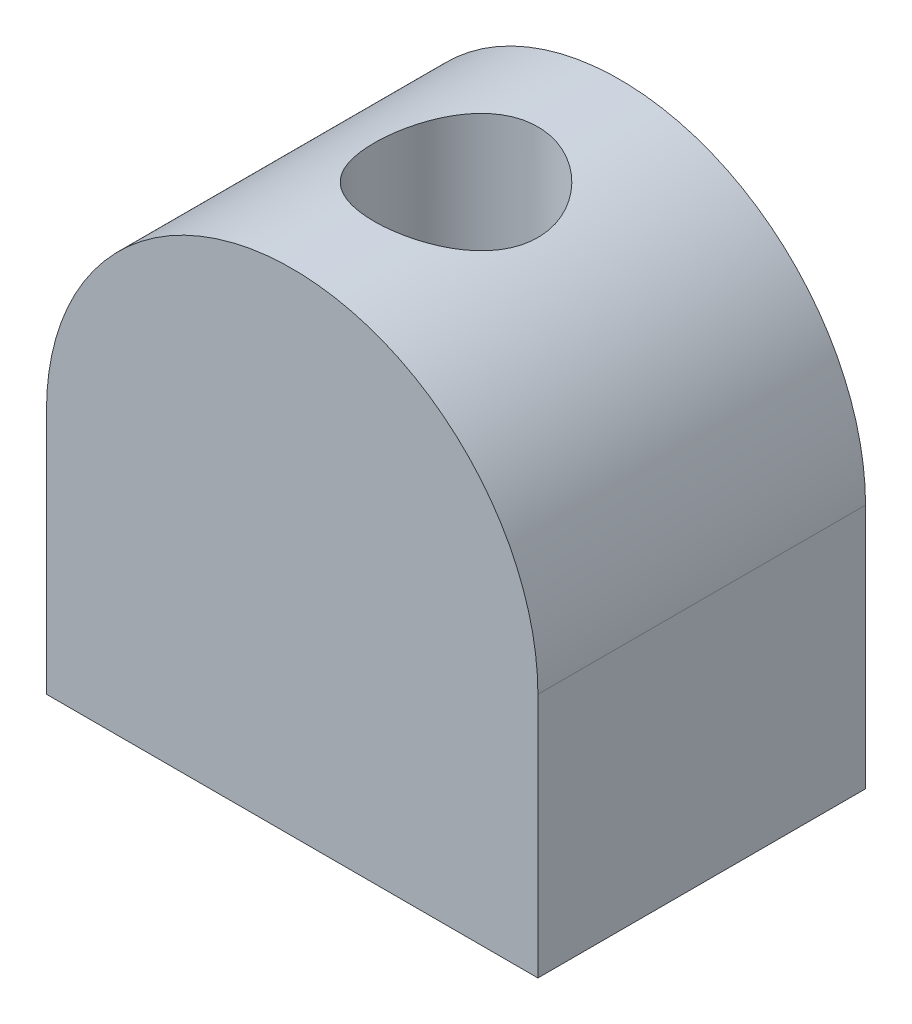
SolidWorks part; units mm, degrees
other "Title Block Table1"
other "DetailItem1"
material "PA Type 6 - Black"
ref_plane "Front Plane" through (0, 0, 0) normal (0, 0, 1) x (1, 0, 0)
ref_plane "Top Plane" through (0, 0, 0) normal (0, 1, 0) x (1, 0, 0)
ref_plane "Right Plane" through (0, 0, 0) normal (1, 0, 0) x (0, 0, -1)
ref_axis "X-Axis" through (-83.7009, 0, 0) along (1, 0, 0)
ref_axis "Y-Axis" through (0, 70.1691, 0) along (0, -1, 0)
ref_axis "Z-Axis" through (0, 0, -88.99) along (0, 0, 1)
sketch "Sketch1" plane through (0, 0, 0) normal (0, 0, 1) x (1, 0, 0)
  line L11 (-15, 7.5) -> (-15, -7.5)
  line L12 (-15, -7.5) -> (15, -7.5)
  line L13 (15, 7.5) -> (15, -7.5)
  line L14 (-15, 7.5) -> (15, -7.5) construction
  line L15 (-15, -7.5) -> (15, 7.5) construction
  arc A3 (15, 7.5) -> (-15, 7.5) centre (0, 7.5) ccw
  point P0 (0, 0)
  point P1 (-12.2822, -1.5264)
  point P2 (0, 0)
  point P3 (0, 0)
  point P13 (0, 0)
  dimension "D1" = 15
  dimension "D2" = 30
extrude "Boss-Extrude1" add sketch "Sketch1" along normal mid plane 20
ref_plane "Plane1" through (0, 22.5, 0) normal (0, 1, 0) x (1, 0, 0)
hole_wizard "CBORE for M5 Hex Socket Head Cap Screw1" positions "Sketch2" profile "Sketch4" counterbore size "M5" standard "DIN" end condition through all
sketch "Sketch2" plane through (0, 22.5, 0) normal (0, 1, 0) x (1, 0, 0)
  point P0 (0, 0)
sketch "Sketch4" plane through (0, 22.5, 0) normal (1, 0, 0) x (0, 0, 1)
  line L0 (0, 0) -> (0, 30)
  line L1 (0, 30) -> (2.75, 30)
  line L3 (2.75, 30) -> (2.75, 8)
  line L4 (2.75, 8) -> (5, 8)
  line L5 (5, 8) -> (5, 0)
  line L7 (5, 0) -> (0, 0)
  line L11 (0, -6.35) -> (0, 107.95) construction
  dimension "Thru Hole Dia." = 5.5
  dimension "Thru Hole Depth" = 30
  dimension "C'Bore Dia." = 10
  dimension "C'Bore Depth" = 8
